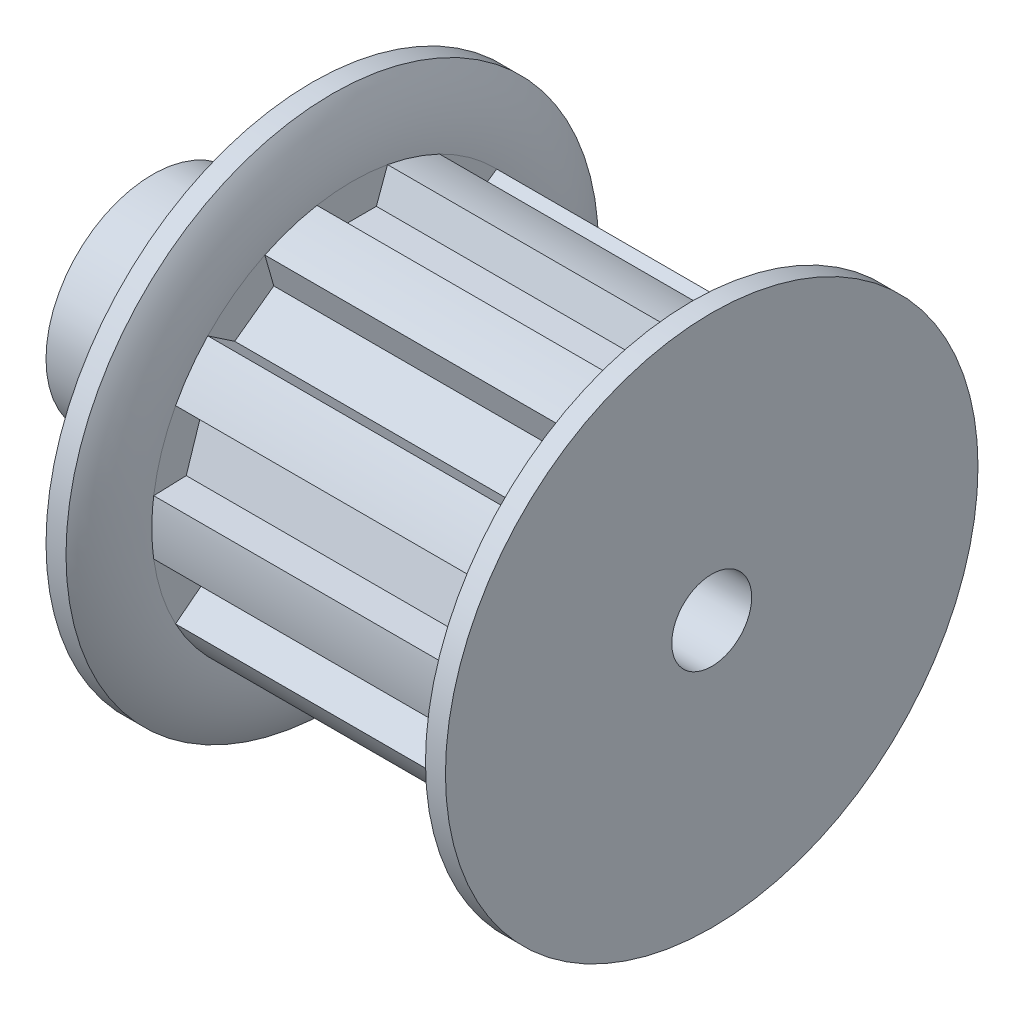
SolidWorks part; units mm, degrees
ref_plane "Front Plane" through (0, 0, 0) normal (0, 0, 1) x (1, 0, 0)
ref_plane "Top Plane" through (0, 0, 0) normal (0, 1, 0) x (1, 0, 0)
ref_plane "Right Plane" through (0, 0, 0) normal (1, 0, 0) x (0, 0, -1)
sketch "Sketch1" plane through (0, 0, 0) normal (1, 0, 0) x (0, 0, -1)
  line L3 (0, 0) -> (0, 6.325) construction
  line L6 (0, 6.325) -> (0, 7.525) construction
  line L7 (-1.325, 7.4074) -> (-0.9072, 6.2596)
  line L8 (1.325, 7.4074) -> (0.9072, 6.2596)
  line L9 (0, -2.2) -> (0, -3.2) construction
  line L10 (0, 8.025) -> (0, 7.525) construction
  line L12 (-0.9072, 6.2596) -> (0.9072, 6.2596)
  line L15 (0, 0) -> (0, -2.2) construction
  circle A0 centre (0, 0) radius 8.025 construction
  circle A1 centre (0, 0) radius 6.325 construction
  arc A7 (1.325, 7.4074) -> (-1.325, 7.4074) centre (0, 0) ccw
  dimension "PD" = 16.05
  dimension "D1" = 40
  dimension "D3" = 0.5
  dimension "D2" = 1.2
  dimension "D4" = 2.65
sketch "Sketch2" plane through (0, 0, 0) normal (0, 0, 1) x (1, 0, 0)
  line L0 (-10.5, 0) -> (10.5, 0) construction
  line L1 (-10.5, 2) -> (10.5, 2)
  line L2 (-10.5, 2) -> (-10.5, 4)
  line L3 (-4.5, 10) -> (-3.75, 10)
  line L4 (-3, 7.525) -> (-4.5, 7.525) construction
  line L5 (9.75, 7.525) -> (9.75, 10) construction
  line L6 (-3, 7.525) -> (9, 7.525)
  line L8 (9, 7.525) -> (10.5, 7.525) construction
  line L9 (9.75, 10) -> (10.5, 10)
  line L10 (10.5, 10) -> (10.5, 2)
  line L12 (-7.5, 4) -> (-7.5, 2) construction
  line L13 (-4.5, 10) -> (-4.5, 4)
  line L14 (-4.5, 4) -> (-10.5, 4)
  arc A0 (9, 7.525) -> (9.75, 10) centre (13.4588, 7.525) cw
  arc A1 (-3, 7.525) -> (-3.75, 10) centre (-7.4588, 7.525) ccw
  point P19 (-3, 7.525)
  point P20 (9, 7.525)
  dimension "Bore Size" = 4
  dimension "Overall Width" = 21
  dimension "Inside Width" = 12
  dimension "Outside Width" = 15
  dimension "Hub Dia" = 8
  dimension "OD" = 20
sketch "Sketch6" plane through (0, 0, 0) normal (0, 0, 1) x (1, 0, 0)
  line L0 (9.75, 10) -> (10.5, 10) construction
  line L1 (-3, 7.525) -> (9, 7.525) construction
  line L2 (-4.5, 10) -> (-3.75, 10) construction
  line L3 (-4.5, 10) -> (-4.5, 4) construction
  line L4 (-4.5, 4) -> (-10.5, 4) construction
  line L5 (-10.5, 2) -> (-10.5, 4) construction
  line L6 (-10.5, 2) -> (10.5, 2) construction
  line L7 (10.5, 10) -> (10.5, 2) construction
  line L8 (9.75, 10) -> (10.5, 10)
  line L9 (-3, 7.525) -> (9, 7.525)
  line L10 (-4.5, 10) -> (-3.75, 10)
  line L11 (-4.5, 10) -> (-4.5, 4)
  line L12 (-4.5, 4) -> (-10.5, 4)
  line L13 (-10.5, 2) -> (-10.5, 4)
  line L14 (-10.5, 2) -> (10.5, 2)
  line L15 (10.5, 10) -> (10.5, 2)
  arc A0 (9.75, 10) -> (9, 7.525) centre (13.4588, 7.525) ccw construction
  arc A1 (-3, 7.525) -> (-3.75, 10) centre (-7.4588, 7.525) ccw construction
  arc A2 (9.75, 10) -> (9, 7.525) centre (13.4588, 7.525) ccw
  arc A3 (-3, 7.525) -> (-3.75, 10) centre (-7.4588, 7.525) ccw
revolve "Revolve1" add sketch "Sketch6" angle 360 about L0
sketch "Sketch3" plane through (0, 0, 0) normal (1, 0, 0) x (0, 0, -1)
  line L2 (-1.325, 7.4074) -> (-0.9072, 6.2596) construction
  line L3 (-0.9072, 6.2596) -> (0.9072, 6.2596) construction
  line L4 (1.325, 7.4074) -> (0.9072, 6.2596) construction
  line L5 (-1.325, 7.4074) -> (-0.9072, 6.2596)
  line L6 (-0.9072, 6.2596) -> (0.9072, 6.2596)
  line L7 (1.325, 7.4074) -> (0.9072, 6.2596)
  arc A1 (1.325, 7.4074) -> (-1.325, 7.4074) centre (0, 0) ccw construction
  arc A2 (1.325, 7.4074) -> (-1.325, 7.4074) centre (0, 0) ccw
extrude "Cut-Extrude1" cut sketch "Sketch3" along normal up to vertex (9 mm away) from vertex up to point (9, 7.525, 0) starting at point (-3, 7.525, 0)
pattern_circular "CirPattern1" count 10 over 360 about axis through (-10.5, 0, 0) along (-1, 0, 0) of "Cut-Extrude1"
sketch "Sketch5" plane through (0, 0, 0) normal (0, 0, 1) x (1, 0, 0)
  line L0 (-10.5, 0) -> (10.5, 0) construction
  point P0 (9, 0)
ref_axis "Center Axis 1" through (10.5, 0, 0) along (-1, 0, 0)
sketch "Sketch7" plane through (0, 0, 0) normal (1, 0, 0) x (0, 0, -1)
  circle A0 centre (0, 0) radius 1.5
  circle A1 centre (0, 0) radius 2.3835
  dimension "D1" = 3
extrude "Boss-Extrude1" add sketch "Sketch7" against normal up to surface (10.5 mm away) from surface up to face at (-10.5, 0, 2) starting at face at (10.5, 0, 10)
equation "\"D3@Sketch1\" = \"ht@Sketch1\" / 2"
equation "\"D2@Sketch1\" = \"hs@Sketch1\" - \"ht@Sketch1\""
